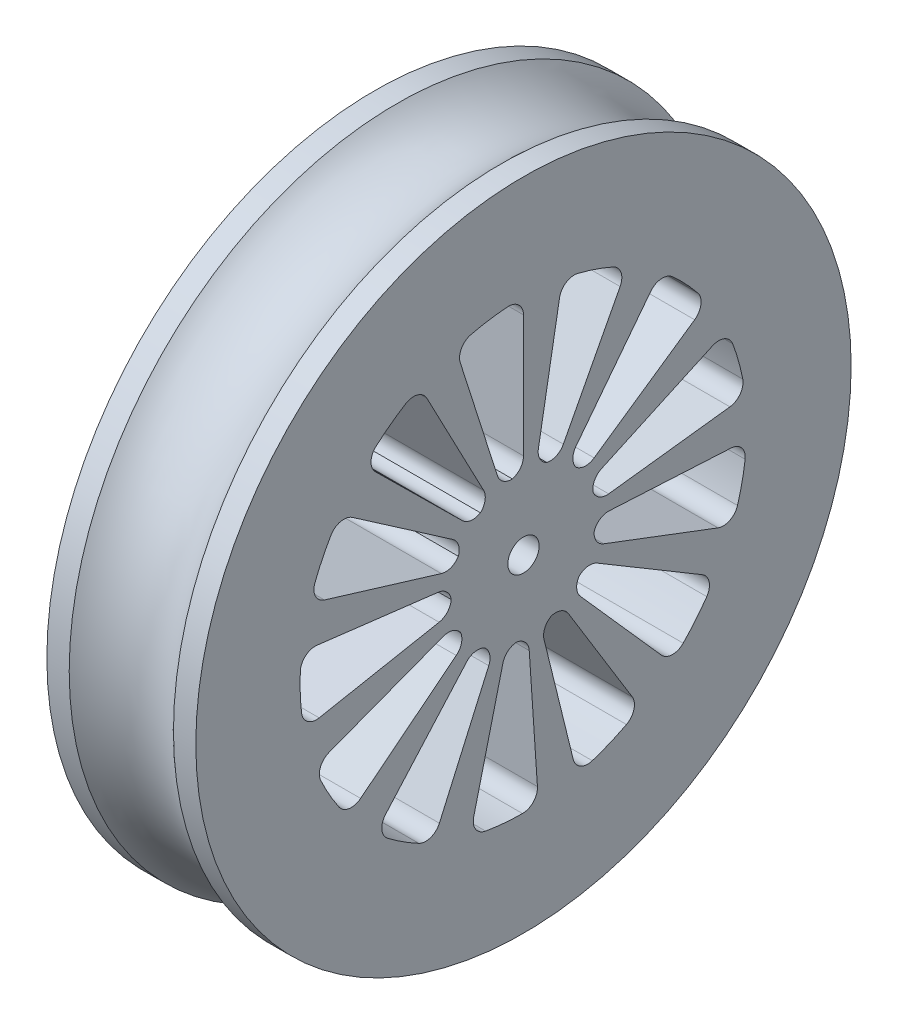
SolidWorks part; units mm, degrees
ref_plane "Front Plane" through (0, 0, 0) normal (0, 0, 1) x (1, 0, 0)
ref_plane "Top Plane" through (0, 0, 0) normal (0, 1, 0) x (1, 0, 0)
ref_plane "Right Plane" through (0, 0, 0) normal (1, 0, 0) x (0, 0, -1)
sketch "Sketch1" plane through (0, 0, 0) normal (0, 0, 1) x (1, 0, 0)
  line L0 (0, 0) -> (10, 0)
  line L1 (0, 0) -> (0, 22)
  line L2 (10, 22) -> (10, 0)
  line L3 (0, 0) -> (34.8651, 0) construction
  line L4 (0, 22) -> (1.5, 22)
  line L5 (10, 22) -> (8.5, 22)
  arc A1 (1.5, 22) -> (8.5, 22) centre (5, 25.5707) ccw
  dimension "D3" = 1.5
  dimension "D4" = 1.5
  dimension "D5" = 5
  dimension "D1" = 10
  dimension "D2" = 22
revolve "Revolve2" add sketch "Sketch1" angle 360 about L3
sketch "Sketch2" plane through (10, 0, 0) normal (1, 0, 0) x (0, 0, -1)
  circle A0 centre (0, 0) radius 1.05
  dimension "D1" = 2.1
extrude "Cut-Extrude1" cut sketch "Sketch2" against normal blind 10 contours A0
sketch "Sketch3" plane through (10, 0, 0) normal (1, 0, 0) x (0, 0, -1)
  line L0 (0, 0) -> (0, 23.0393) construction
  line L1 (0, 4.8503) -> (0, 15)
  line L2 (0.8423, 4.7766) -> (2.6047, 14.7721)
  line L3 (2.9656, 3.8381) -> (9.1713, 11.8696)
  line L4 (2.2541, 4.2948) -> (6.9708, 13.2818)
  line L5 (4.4096, 2.0203) -> (13.6369, 6.2479)
  line L6 (3.9917, 2.7553) -> (12.3448, 8.521)
  line L7 (4.8433, -0.2603) -> (14.9784, -0.8051)
  line L8 (4.815, 0.5846) -> (14.8906, 1.8081)
  line L9 (4.1676, -2.4813) -> (12.8885, -7.6737)
  line L10 (4.5351, -1.7199) -> (14.0252, -5.3191)
  line L11 (2.5371, -4.1339) -> (7.8461, -12.7843)
  line L12 (3.2164, -3.6305) -> (9.9468, -11.2277)
  line L13 (0.3253, -4.8394) -> (1.0062, -14.9662)
  line L14 (1.1608, -4.7094) -> (3.5897, -14.5641)
  line L15 (-1.9609, -4.4363) -> (-6.0642, -13.7195)
  line L16 (-1.1608, -4.7094) -> (-3.5897, -14.5641)
  line L17 (-3.7979, -3.0169) -> (-11.7454, -9.3298)
  line L18 (-3.2164, -3.6305) -> (-9.9468, -11.2277)
  line L19 (-4.7649, -0.9063) -> (-14.7358, -2.8028)
  line L20 (-4.5351, -1.7199) -> (-14.0252, -5.3191)
  line L21 (-4.6403, 1.4119) -> (-14.3504, 4.3663)
  line L22 (-4.815, 0.5846) -> (-14.8906, 1.8081)
  line L23 (-3.4526, 3.4066) -> (-10.6776, 10.5352)
  line L24 (-3.9917, 2.7553) -> (-12.3448, 8.521)
  line L25 (-1.474, 4.6209) -> (-4.5586, 14.2905)
  line L26 (-2.2541, 4.2948) -> (-6.9708, 13.2818)
  circle A0 centre (0, 0) radius 15
  circle A1 centre (0, 0) radius 4.8503
  point P59 (0, 0)
  dimension "D1" = 30
  dimension "D2" = 10
  dimension "D3" = 13
extrude "Cut-Extrude2" cut sketch "Sketch3" against normal through all contours A1 L4 A0 L2 | A1 L6 A0 L3 | A1 L8 A0 L5 | A1 L10 A0 L7 | A1 L12 A0 L9 | A1 L14 A0 L11 | A1 L16 A0 L13 | A1 L18 A0 L15 | A1 L20 A0 L17 | A1 L22 A0 L19 | A1 L24 A0 L21 | A1 L26 A0 L23 | A1 L1 A0 L25 region at (10, 10.6194, 1.6527) region at (10, 10.1711, -3.4717) region at (10, 8.635, 6.3985) region at (10, 7.3927, -7.8008) region at (10, 4.6724, 9.6785) region at (10, 2.9207, -10.3428) region at (10, -0.3607, 10.7412) region at (10, -2.2204, -10.5154) region at (10, -5.311, 9.3433) region at (10, -6.8528, -8.2791) region at (10, -9.0447, 5.8049) region at (10, -9.9153, -4.1461) region at (10, -10.7064, 0.9367)
fillet "Fillet1" radius 1 52 edges at (5, 14.2905, 4.5586) (5, 14.7721, -2.6047) (5, 10.5352, 10.6776) (5, 4.3663, 14.3504) (5, 1.8081, 14.8906) (5, -5.3191, 14.0252) (5, -11.2277, 9.9468) (5, -14.5641, 3.5897) (5, -14.5641, -3.5897) (5, 11.8696, -9.1713) (5, -5.3191, -14.0252) (5, -0.8051, -14.9784) (5, 1.8081, -14.8906) (5, 6.2479, -13.6369) (5, 8.521, -12.3448) (5, 13.2818, -6.9708) (5, 15, 0) (5, 13.2818, 6.9708) (5, 8.521, 12.3448) (5, -2.8028, 14.7358) (5, -9.3298, 11.7454) (5, -13.7195, 6.0642) (5, -14.9662, -1.0062) (5, -12.7843, -7.8461) (5, -11.2277, -9.9468) (5, -7.6737, -12.8885) (5, 4.6209, 1.474) (5, 4.8503, 0) (5, 3.4066, 3.4526) (5, 4.2948, 2.2541) (5, 1.4119, 4.6403) (5, 2.7553, 3.9917) (5, -0.9063, 4.7649) (5, 0.5846, 4.815) (5, -3.0169, 3.7979) (5, -1.7199, 4.5351) (5, -3.6305, 3.2164) (5, -4.4363, 1.9609) (5, -4.7094, 1.1608) (5, -4.8394, -0.3253) (5, -4.7094, -1.1608) (5, -4.1339, -2.5371) (5, -3.6305, -3.2164) (5, -2.4813, -4.1676) (5, -1.7199, -4.5351) (5, -0.2603, -4.8433) (5, 0.5846, -4.815) (5, 2.0203, -4.4096) (5, 2.7553, -3.9917) (5, 4.7766, -0.8423) (5, 4.2948, -2.2541) (5, 3.8381, -2.9656)
sketch "Sketch4" plane through (10, 0, 0) normal (1, 0, 0) x (0, 0, -1)
